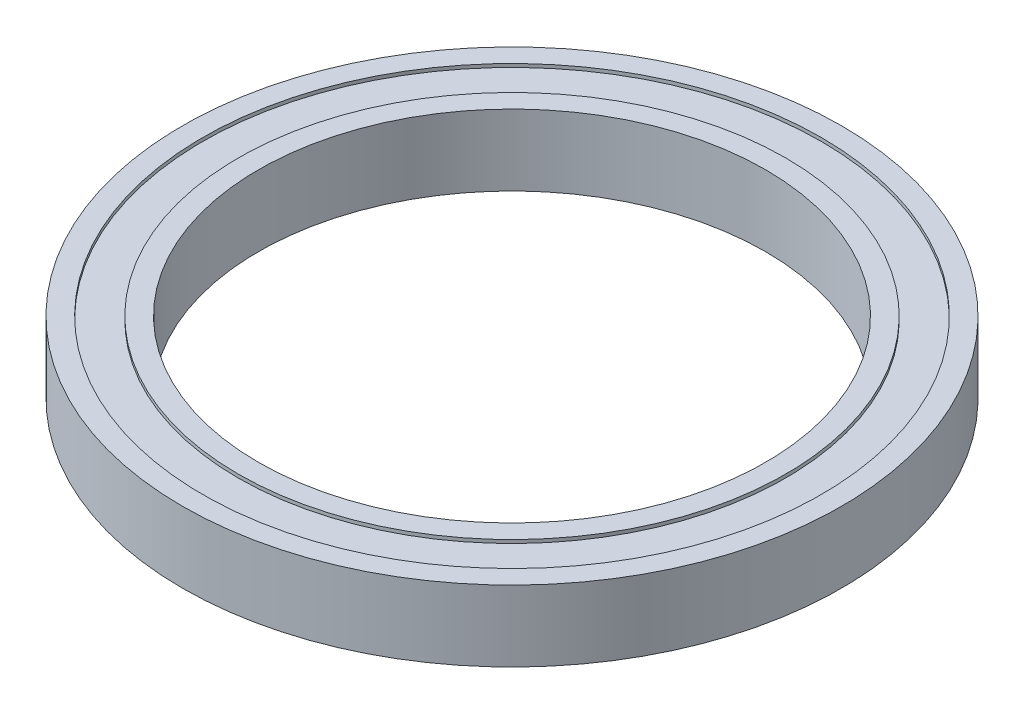
SolidWorks part; units mm, degrees
material "Alloy Steel"
ref_plane "Front Plane" through (0, 0, 0) normal (0, 0, 1) x (1, 0, 0)
ref_plane "Top Plane" through (0, 0, 0) normal (0, 1, 0) x (1, 0, 0)
ref_plane "Right Plane" through (0, 0, 0) normal (1, 0, 0) x (0, 0, -1)
sketch "Sketch1" plane through (0, 0, 0) normal (0, 0, 1) x (1, 0, 0)
  line L0 (25, 0) -> (27, 0)
  line L1 (27, 0) -> (27, 0.3388)
  line L2 (27, 0.3388) -> (30.5, 0.3388)
  line L3 (30.5, 0.3388) -> (30.5, 0)
  line L4 (30.5, 0) -> (32.5, 0)
  line L5 (32.5, 0) -> (32.5, 7)
  line L6 (25, 0) -> (25, 7)
  line L7 (25, 3.5) -> (32.5, 3.5) construction
  line L8 (30.5, 7) -> (32.5, 7)
  line L9 (30.5, 6.6612) -> (30.5, 7)
  line L10 (27, 6.6612) -> (30.5, 6.6612)
  line L11 (27, 7) -> (27, 6.6612)
  line L12 (25, 7) -> (27, 7)
  line L13 (0, 0) -> (0, 19.95) construction
  dimension "D1" = 7
  dimension "D2" = 7.5
  dimension "D3" = 50
  dimension "D4" = 2
revolve "Revolve1" add sketch "Sketch1" angle 360 about L13
